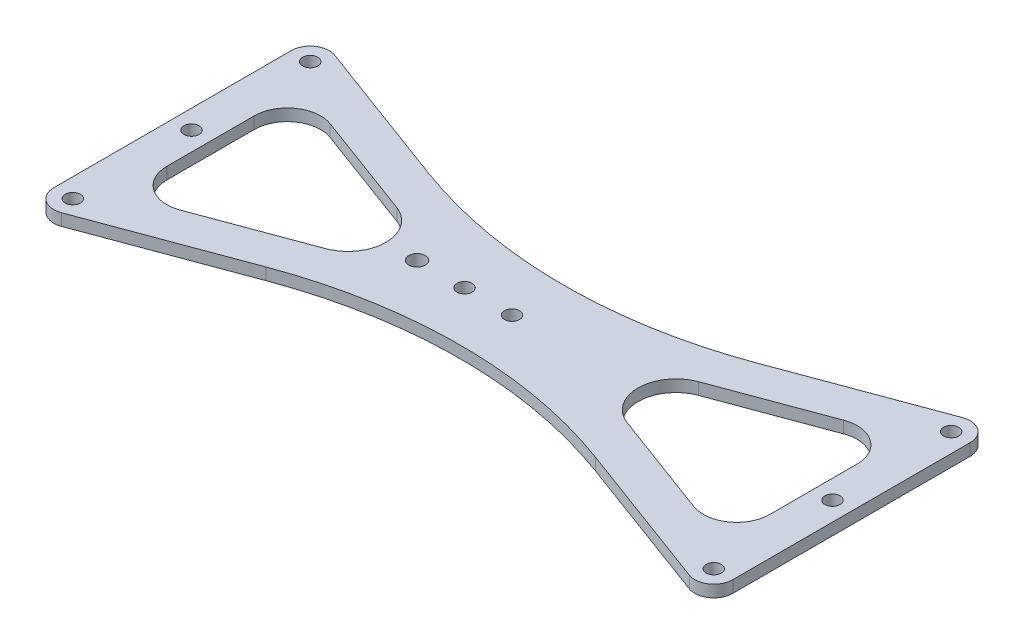
SolidWorks part; units mm, degrees
ref_plane "Front Plane" through (0, 0, 0) normal (0, 0, 1) x (1, 0, 0)
ref_plane "Top Plane" through (0, 0, 0) normal (0, 1, 0) x (1, 0, 0)
ref_plane "Right Plane" through (0, 0, 0) normal (1, 0, 0) x (0, 0, -1)
sketch "Sketch1" plane through (0, 0, 0) normal (0, 1, 0) x (1, 0, 0)
  line L0 (-85.725, 31.75) -> (85.725, -31.75) construction
  line L1 (85.725, 31.75) -> (-85.725, -31.75) construction
  line L2 (-85.725, 31.75) -> (-85.725, -31.75) construction
  line L3 (85.725, 31.75) -> (85.725, -31.75) construction
  line L4 (87.4894, 26.9862) -> (-83.9606, -36.5138)
  line L5 (-83.9606, 36.5138) -> (87.4894, -26.9862)
  line L6 (83.9606, 36.5138) -> (-87.4894, -26.9862)
  line L7 (-87.4894, 26.9862) -> (83.9606, -36.5138)
  line L8 (-90.805, 31.75) -> (-90.805, -31.75)
  line L9 (-80.645, 31.75) -> (-80.645, -31.75)
  line L10 (80.645, 31.75) -> (80.645, -31.75)
  line L11 (90.805, 31.75) -> (90.805, -31.75)
  line L12 (0, 0) -> (-25.4, 0) construction
  circle A0 centre (-85.725, -31.75) radius 2.032
  circle A1 centre (-85.725, 31.75) radius 2.032
  circle A2 centre (-85.725, 0) radius 2.032
  circle A3 centre (85.725, 31.75) radius 2.032
  circle A4 centre (85.725, 0) radius 2.032
  circle A5 centre (85.725, -31.75) radius 2.032
  arc A6 (87.4894, 26.9862) -> (83.9606, 36.5138) centre (85.725, 31.75) ccw
  arc A7 (-83.9606, -36.5138) -> (-87.4894, -26.9862) centre (-85.725, -31.75) cw
  arc A8 (-83.9606, 36.5138) -> (-87.4894, 26.9862) centre (-85.725, 31.75) ccw
  arc A9 (87.4894, -26.9862) -> (83.9606, -36.5138) centre (85.725, -31.75) cw
  arc A10 (-90.805, 31.75) -> (-80.645, 31.75) centre (-85.725, 31.75) cw
  arc A11 (-90.805, -31.75) -> (-80.645, -31.75) centre (-85.725, -31.75) ccw
  arc A12 (80.645, 31.75) -> (90.805, 31.75) centre (85.725, 31.75) cw
  arc A13 (80.645, -31.75) -> (90.805, -31.75) centre (85.725, -31.75) ccw
  circle A14 centre (0, 0) radius 2.032
  circle A15 centre (-12.7, 0) radius 2.032
  circle A16 centre (-25.4, 0) radius 2.2225
  point P4 (0, 0)
  point P8 (0, 0)
  dimension "D3" = 4.064
  dimension "D10" = 4.064
  dimension "D13" = 4.445
  dimension "D1" = 63.5
  dimension "D2" = 171.45
  dimension "D11" = 12.7
  dimension "D12" = 12.7
  dimension "D4" = 5.08
  dimension "D5" = 5.08
  dimension "D6" = 5.08
  dimension "D7" = 5.08
  dimension "D8" = 5.08
  dimension "D9" = 5.08
extrude "Boss-Extrude1" add sketch "Sketch1" along normal blind 3.175 contours A7 A11 L9 L6 A0 | A8 L8 A7 L6 L9 L7 A2 | A11 L4 L7 L6 L9 | A10 A8 L7 L9 A1 | L5 A10 L9 L7 L6 | A13 L10 L5 L4 L7 | L6 L7 L4 L5 | L10 A12 L6 L5 L4 | L5 A9 L11 A6 L4 L10 A4 | A12 L10 L4 A6 A3 | L10 A13 A9 L5 A5 | L6 A15 L7 | L6 A15 L7 | L7 A15 L6 | A14 region at (90.4223, 0, -28.4806) region at (84.0116, 0, -25.8689) region at (43.9644, 0, -16.476) region at (43.9644, 0, 16.476) region at (7.2162, 0, 2.4466) region at (84.0116, 0, 25.8689) region at (-44.1127, 0, 16.5496) region at (-44.1127, 0, -16.5496) region at (-88.5355, 0, 35.7881) region at (-13.1268, 0, 1.1582) region at (-12.0893, 0, 0) region at (-81.6869, 0, -34.5605) region at (-13.1268, 0, -1.1582) region at (-90.1619, 0, 0) region at (0, 0, 0)
fillet "Fillet1" radius 8.89 4 edges at (-80.645, 1.5875, 24.4513) (-80.645, 1.5875, -24.4513) (80.645, 1.5875, 24.4513) (80.645, 1.5875, -24.4513)
fillet "Fillet2" radius 10.16 2 edges at (14.6265, 1.5875, 0) (-14.6265, 1.5875, 0)
fillet "Fillet3" radius 127 2 edges at (0, 1.5875, 5.4172) (0, 1.5875, -5.4172)
extrude "Cut-Extrude1" cut sketch "Sketch1<3>" along normal through all contours A16 | A15 | A14
sketch "Sketch1<3>" plane through (0, 0, 0) normal (0, 1, 0) x (1, 0, 0) same geometry as "Sketch1"
